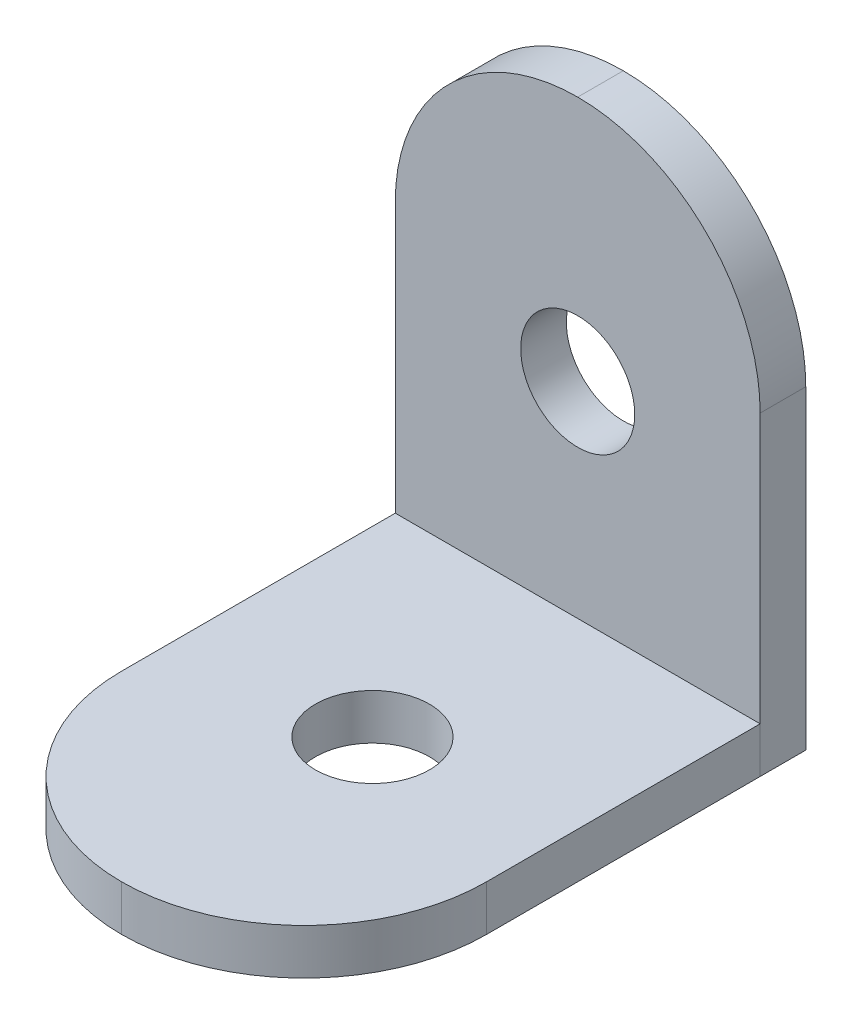
SolidWorks part; units mm, degrees
ref_plane "前视基准面" through (0, 0, 0) normal (0, 0, 1) x (1, 0, 0)
ref_plane "上视基准面" through (0, 0, 0) normal (0, 1, 0) x (1, 0, 0)
ref_plane "右视基准面" through (0, 0, 0) normal (1, 0, 0) x (0, 0, -1)
sketch "草图1" plane through (0, 0, 0) normal (0, 0, 1) x (1, 0, 0)
  line L1 (0, 0) -> (16, 0)
  line L2 (0, 0) -> (0, 2)
  line L3 (0, 2) -> (16, 2)
  line L4 (16, 0) -> (16, 2)
extrude "凸台-拉伸1" add sketch "草图1" along normal blind 20
fillet "圆角1" radius 8 1 edges at (0, 1, 20)
fillet "圆角2" radius 8 1 edges at (16, 1, 20)
sketch "草图2" plane through (0, 0, 0) normal (0, 1, 0) x (1, 0, 0)
  line L1 (0, 0) -> (16, 0)
  line L2 (0, 0) -> (0, 2)
  line L3 (0, 2) -> (16, 2)
  line L4 (16, 0) -> (16, 2)
extrude "凸台-拉伸2" add sketch "草图2" along normal blind 21.8 separate body
fillet "圆角3" radius 8 1 edges at (16, 21.8, -1)
fillet "圆角4" radius 8 1 edges at (0, 21.8, -1)
sketch "草图4" plane through (0, 2, 0) normal (0, 1, 0) x (1, 0, 0)
  line L1 (16, 0) -> (0, 0) construction
  circle A1 centre (8, -9) radius 2.5
  dimension "D1" = 9
extrude "切除-拉伸2" cut sketch "草图4" against normal blind 2
sketch "草图6" plane through (0, 0, 0) normal (0, 0, 1) x (1, 0, 0)
  line L1 (16, 2) -> (0, 2) construction
  circle A1 centre (8, 11) radius 2.5
  dimension "D1" = 9
extrude "切除-拉伸3" cut sketch "草图6" against normal blind 3
